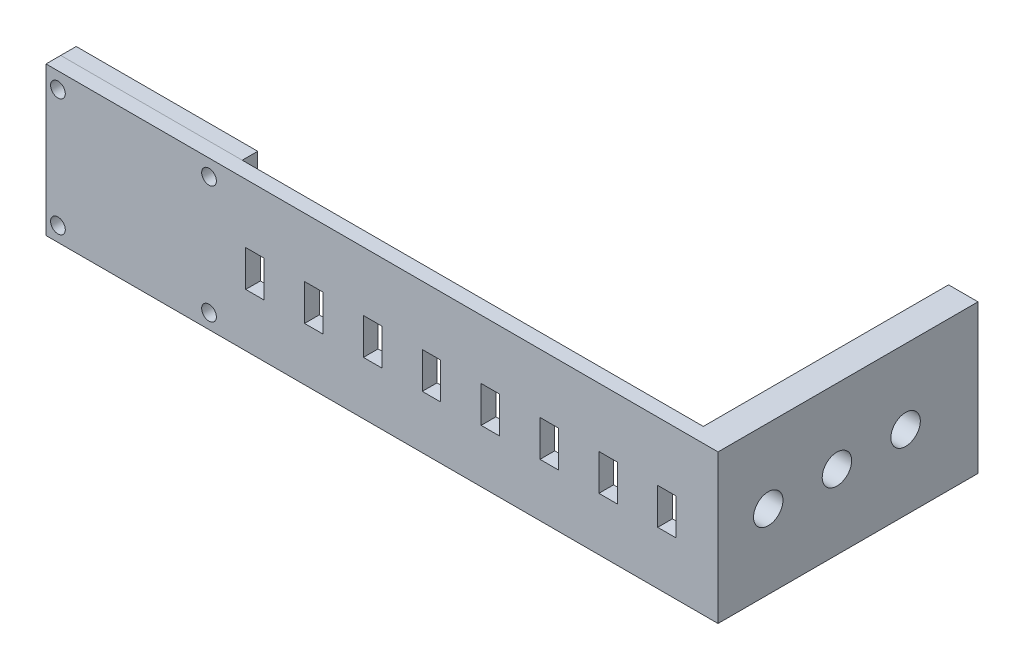
SolidWorks part; units mm, degrees
note: The reader was unsure of these and kept them because the rebuilt part matched: shared geometry of "Sketch1<3>", "Sketch1<4>".
ref_plane "Front Plane" through (0, 0, 0) normal (0, 0, 1) x (1, 0, 0)
ref_plane "Top Plane" through (0, 0, 0) normal (0, 1, 0) x (1, 0, 0)
ref_plane "Right Plane" through (0, 0, 0) normal (1, 0, 0) x (0, 0, -1)
ref_plane "Plane1" through (0, 0, 1.58) normal (0, 0, 1) x (1, 0, 0)
sketch "Sketch1" plane through (0, 0, 1.58) normal (0, 0, 1) x (1, 0, 0)
  line L0 (9.9672, -11.3237) -> (9.9672, 3.8263)
  line L1 (9.9672, 3.8263) -> (-3.2783, 3.8263)
  line L2 (9.9672, 3.8263) -> (59.9672, 3.8263)
  line L3 (17.8226, -2.203) -> (17.8226, -5.9028)
  line L4 (59.9672, 3.8263) -> (59.9672, -11.3237)
  line L5 (-7.473, 3.8263) -> (-8.5328, 3.8263)
  line L6 (-8.5328, 3.8263) -> (-8.5328, -11.3237)
  line L7 (-8.5328, -11.3237) -> (-7.473, -11.3237)
  line L8 (59.9672, -11.3237) -> (9.9672, -11.3237)
  line L9 (17.8226, -2.203) -> (19.7014, -2.203)
  line L10 (9.9672, -3.7487) -> (59.9672, -3.7487) construction
  line L11 (-3.2783, -11.3237) -> (9.9672, -11.3237)
  line L12 (-7.473, 3.8263) -> (-3.2783, 3.8263)
  line L13 (-7.473, -11.3237) -> (-3.2783, -11.3237)
  line L14 (17.8226, -5.9028) -> (19.7014, -5.9028)
  line L15 (19.7014, -2.203) -> (19.7014, -5.9028)
  line L16 (23.8226, -2.203) -> (23.8226, -5.9028)
  line L17 (23.8226, -2.203) -> (25.7014, -2.203)
  line L18 (23.8226, -5.9028) -> (25.7014, -5.9028)
  line L19 (25.7014, -2.203) -> (25.7014, -5.9028)
  line L20 (29.8226, -2.203) -> (29.8226, -5.9028)
  line L21 (29.8226, -2.203) -> (31.7014, -2.203)
  line L22 (29.8226, -5.9028) -> (31.7014, -5.9028)
  line L23 (31.7014, -2.203) -> (31.7014, -5.9028)
  line L24 (35.8226, -2.203) -> (35.8226, -5.9028)
  line L25 (35.8226, -2.203) -> (37.7014, -2.203)
  line L26 (35.8226, -5.9028) -> (37.7014, -5.9028)
  line L27 (11.8226, -2.203) -> (11.8226, -5.9028)
  line L28 (11.8226, -2.203) -> (13.7014, -2.203)
  line L29 (11.8226, -5.9028) -> (13.7014, -5.9028)
  line L30 (13.7014, -2.203) -> (13.7014, -5.9028)
  line L31 (37.7014, -2.203) -> (37.7014, -5.9028)
  line L32 (41.8226, -2.203) -> (41.8226, -5.9028)
  line L33 (41.8226, -2.203) -> (43.7014, -2.203)
  line L34 (41.8226, -5.9028) -> (43.7014, -5.9028)
  line L35 (43.7014, -2.203) -> (43.7014, -5.9028)
  line L36 (47.8226, -2.203) -> (47.8226, -5.9028)
  line L37 (47.8226, -2.203) -> (49.7014, -2.203)
  line L38 (47.8226, -5.9028) -> (49.7014, -5.9028)
  line L39 (49.7014, -2.203) -> (49.7014, -5.9028)
  line L40 (53.8226, -2.203) -> (53.8226, -5.9028)
  line L41 (53.8226, -2.203) -> (55.7014, -2.203)
  line L42 (53.8226, -5.9028) -> (55.7014, -5.9028)
  line L43 (55.7014, -2.203) -> (55.7014, -5.9028)
  line L44 (-8.5328, 1.8263) -> (9.9672, 1.8263)
  line L45 (-8.5328, -9.3237) -> (9.9672, -9.3237)
  line L51 (-7.3165, 2.1763) -> (-7.3165, -9.8237) construction
  line L52 (59.9672, 3.8263) -> (56.9672, 3.8263)
  line L53 (59.9672, 3.8263) -> (59.9672, -11.3237)
  line L54 (59.9672, -11.3237) -> (56.9672, -11.3237)
  line L55 (56.9672, 3.8263) -> (56.9672, -11.3237)
  line L56 (-7.3165, -9.8237) -> (8.0835, -9.8237) construction
  line L57 (8.0835, -9.8237) -> (8.0835, 2.1763) construction
  line L58 (8.0835, 2.1763) -> (-7.3165, 2.1763) construction
  circle A0 centre (8.0835, 2.1763) radius 0.75
  circle A1 centre (8.0835, -9.8237) radius 0.75
  circle A2 centre (-7.3165, -9.8237) radius 0.75
  circle A3 centre (-7.3165, 2.1763) radius 0.75
  dimension "D6" = 1.5
  dimension "D7" = 1.5
  dimension "D1" = 50
  dimension "D3" = 3
  dimension "D4" = 15.15
  dimension "D5" = 18.5
  dimension "D2" = 12
  dimension "D8" = 15.4
  dimension "D9" = 2
  dimension "D10" = 2
extrude "Boss-Extrude1" add sketch "Sketch1" against normal blind 1.58 contours L44 A3 A0 L0 L1 L12 L5 L6 | L45 A2 L6 L7 L13 L11 L0 A1
extrude "Boss-Extrude2" add sketch "Sketch1<3>" along normal blind 1.5
sketch "Sketch1<3>" plane through (0, 0, 1.58) normal (0, 0, 1) x (1, 0, 0) same geometry as "Sketch1"
extrude "Boss-Extrude3" add sketch "Sketch1<4>" along normal blind 1.5 and the other way blind 25 contours L2 L55 L8 L4
sketch "Sketch1<4>" plane through (0, 0, 1.58) normal (0, 0, 1) x (1, 0, 0) same geometry as "Sketch1"
sketch "Sketch2" plane through (56.9672, 0, 0) normal (-1, 0, 0) x (0, 0, 1)
  line L0 (1.58, -3.7487) -> (-23.42, -3.7487) construction
  line L1 (1.58, 3.8263) -> (1.58, -11.3237) construction
  line L2 (-23.42, 3.8263) -> (-23.42, -11.3237) construction
  circle A0 centre (-2.0402, -3.7487) radius 1.5
  circle A1 centre (-9.0402, -3.7487) radius 1.5
  circle A2 centre (-16.0402, -3.7487) radius 1.5
  dimension "D1" = 3
  dimension "D2" = 3
extrude "Cut-Extrude1" cut sketch "Sketch2" against normal blind 4.5
